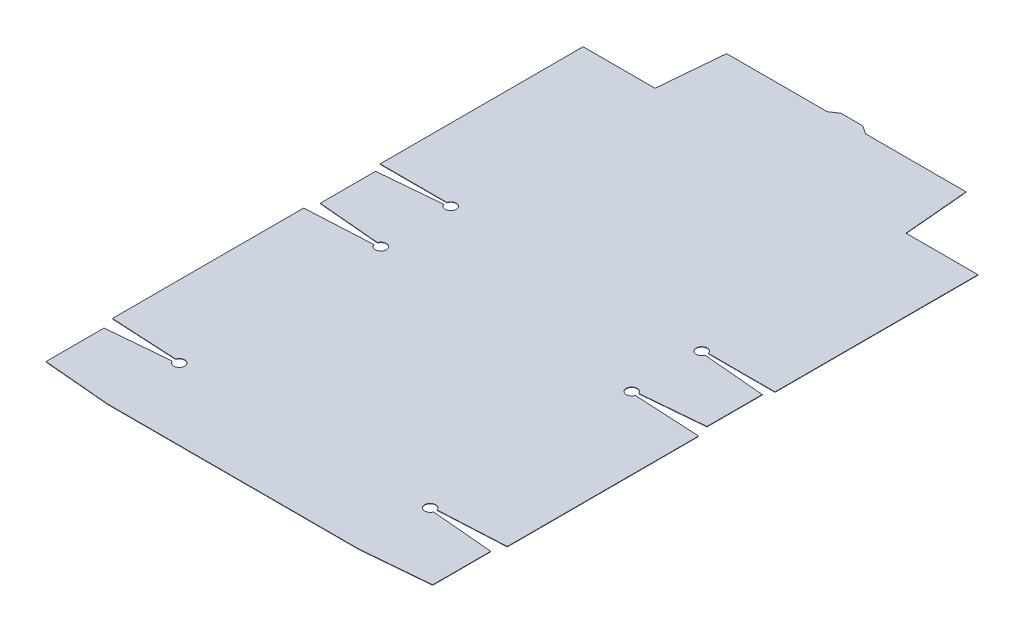
SolidWorks part; units mm, degrees
material "CHIP BOARD"
ref_plane "Front Plane" through (0, 0, 0) normal (0, 0, 1) x (1, 0, 0)
ref_plane "Top Plane" through (0, 0, 0) normal (0, 1, 0) x (1, 0, 0)
ref_plane "Right Plane" through (0, 0, 0) normal (1, 0, 0) x (0, 0, -1)
sketch "Sketch1" plane through (0, 0, 0) normal (0, 1, 0) x (1, 0, 0)
  line L0 (145.2563, 434.1812) -> (138.0341, 516.7312)
  line L1 (-146.05, 116.6813) -> (146.05, 116.6813) construction
  line L3 (145.2562, -199.2313) -> (223.8375, -192.3563)
  line L5 (-146.05, -116.6813) -> (146.05, -116.6813) construction
  line L6 (228.6, 434.1812) -> (228.6, 199.2312) construction
  line L7 (-145.2562, -199.2313) -> (145.2562, -199.2313)
  line L8 (146.05, 199.2312) -> (146.05, 116.6812) construction
  line L9 (-145.2562, -199.2313) -> (-223.8375, -192.3563)
  line L10 (228.6, -110.7237) -> (145.1732, -115.0959)
  line L11 (-228.6, -110.7237) -> (-145.1732, -115.0959)
  line L12 (-228.6, -110.7237) -> (-228.6, 110.7237)
  line L14 (223.8375, -192.3563) -> (223.8375, -125.1498)
  line L15 (223.8375, -125.1498) -> (145.1179, -118.2627)
  line L16 (-138.0341, 516.7312) -> (-145.2563, 434.1812)
  line L18 (145.2563, 434.1812) -> (228.6, 434.1812)
  line L19 (145.1179, 196.0623) -> (223.8375, 189.1752)
  line L21 (228.6, -110.7237) -> (228.6, 110.7237)
  line L22 (-145.2563, 434.1812) -> (-228.6, 434.1812)
  line L23 (228.6, 199.2312) -> (145.2562, 199.2312)
  line L24 (-228.6, 110.7237) -> (-145.1732, 115.0959)
  line L25 (223.8375, 189.1752) -> (223.8375, 125.1498)
  line L26 (228.6, 110.7237) -> (145.1732, 115.0959)
  line L27 (223.8375, 125.1498) -> (145.1179, 118.2627)
  line L28 (-228.6, 199.2312) -> (-145.2562, 199.2312)
  line L29 (0, 0) -> (0, 116.6812) construction
  line L32 (-145.1179, 196.0623) -> (-223.8375, 189.1752)
  line L33 (146.05, 116.6813) -> (146.05, -116.6813) construction
  line L34 (-146.05, 199.2312) -> (228.6, 199.2312) construction
  line L35 (145.2562, -116.6813) -> (145.2562, -199.2313) construction
  line L36 (-145.2562, -199.2313) -> (-145.2562, -116.6813) construction
  line L37 (-223.8375, 189.1752) -> (-223.8375, 125.1498)
  line L38 (-223.8375, 125.1498) -> (-145.1179, 118.2627)
  line L39 (228.6, 199.2312) -> (228.6, 434.1812)
  line L40 (-146.05, -116.6813) -> (-146.05, 116.6813) construction
  line L41 (-146.05, 116.6812) -> (-146.05, 199.2312) construction
  line L42 (-228.6, 434.1812) -> (-228.6, 199.2312) construction
  line L43 (-228.6, 434.1812) -> (228.6, 434.1812) construction
  line L44 (-138.0341, 516.7312) -> (138.0341, 516.7312)
  line L45 (0, 0) -> (-146.05, 0) construction
  line L48 (-228.6, 434.1812) -> (-228.6, 199.2312)
  line L49 (-223.8375, -192.3563) -> (-223.8375, -125.1498)
  line L50 (-223.8375, -125.1498) -> (-145.1179, -118.2627)
  arc A0 (-145.1179, -118.2627) -> (-145.1732, -115.0959) centre (-145.2562, -116.6813) ccw
  arc A1 (145.1732, -115.0959) -> (145.1179, -118.2627) centre (145.2562, -116.6813) ccw
  arc A2 (145.1179, 118.2627) -> (145.1732, 115.0959) centre (145.2562, 116.6812) ccw
  arc A3 (-145.1732, 115.0959) -> (-145.1179, 118.2627) centre (-145.2562, 116.6812) ccw
  arc A4 (-145.1179, 196.0623) -> (-145.2562, 199.2312) centre (-145.2562, 197.6437) ccw
  arc A5 (145.2562, 199.2312) -> (145.1179, 196.0623) centre (145.2562, 197.6437) ccw
  point P4 (0, 116.6812)
  dimension "D5" = 1.5875
  dimension "D3" = 82.55
  dimension "D4" = 447.675
  dimension "D6" = 93
  dimension "D7" = 5
  dimension "D8" = 233.3625
  dimension "D9" = 82.55
  dimension "D10" = 95
  dimension "D11" = 234.95
  dimension "D12" = 82.55
  dimension "D13" = 82.55
  dimension "D14" = 95
  dimension "D15" = 93
  dimension "D16" = 0.7937
  dimension "D17" = 715.9625
  dimension "D18" = 93
  dimension "D19" = 95
  dimension "D20" = 292.1
  dimension "D21" = 95
  dimension "D23" = 292.1
extrude "Extrude1" add sketch "Sketch1" along normal blind 0.4572
sketch "Sketch2" plane through (0, 0.4572, 0) normal (0, 1, 0) x (1, 0, 0)
  circle A0 centre (-145.2562, 116.6812) radius 6.35
  circle A1 centre (-145.2562, -116.6813) radius 6.35
  circle A2 centre (145.2562, -116.6813) radius 6.35
  circle A3 centre (145.2562, 116.6812) radius 6.35
  circle A4 centre (-145.2562, 197.6437) radius 6.35
  circle A5 centre (145.2562, 197.6437) radius 6.35
  arc A6 (145.1732, -115.0959) -> (145.1179, -118.2627) centre (145.2562, -116.6813) ccw construction
  arc A7 (-145.1179, 196.0623) -> (-145.2562, 199.2312) centre (-145.2562, 197.6437) ccw construction
  arc A8 (-145.1732, 115.0959) -> (-145.1179, 118.2627) centre (-145.2562, 116.6812) ccw construction
  arc A9 (-145.1179, -118.2627) -> (-145.1732, -115.0959) centre (-145.2562, -116.6813) ccw construction
  arc A10 (145.1179, 118.2627) -> (145.1732, 115.0959) centre (145.2562, 116.6812) ccw construction
  arc A11 (145.2562, 199.2312) -> (145.1179, 196.0623) centre (145.2562, 197.6437) ccw construction
  dimension "D1" = 12.7
extrude "Extrude2" cut sketch "Sketch2" against normal up to next
sketch "Sketch12" plane through (0, 0.4572, 0) normal (0, 1, 0) x (1, 0, 0)
  line L0 (-138.5896, 510.3813) -> (-22.225, 510.3813)
  line L1 (-138.0341, 516.7312) -> (-145.2563, 434.1812) construction
  line L2 (-22.225, 510.3813) -> (-12.7, 516.7312)
  line L3 (138.0341, 516.7312) -> (-138.0341, 516.7312) construction
  line L4 (12.7, 516.7312) -> (22.225, 510.3813)
  line L5 (22.225, 510.3813) -> (138.5896, 510.3813)
  line L6 (145.2563, 434.1812) -> (138.0341, 516.7312) construction
  line L7 (138.5896, 510.3813) -> (138.0341, 516.7312)
  line L8 (138.0341, 516.7312) -> (12.7, 516.7312)
  line L9 (-12.7, 516.7312) -> (-138.0341, 516.7312)
  line L10 (-138.0341, 516.7312) -> (-138.5896, 510.3813)
  dimension "D1" = 6.35
  dimension "D2" = 25.4
  dimension "D3" = 44.45
extrude "Extrude3" cut sketch "Sketch12" against normal up to next
sketch "Sketch13" plane through (0, 0.4572, 0) normal (0, 1, 0) x (1, 0, 0)
  line L0 (-61.9125, -199.2313) -> (-55.5625, -186.5313)
  line L1 (-145.2562, -199.2313) -> (145.2562, -199.2313) construction
  line L2 (-55.5625, -186.5313) -> (-49.2125, -199.2313)
  line L3 (-49.2125, -199.2313) -> (-61.9125, -199.2313)
  line L4 (49.2125, -199.2313) -> (55.5625, -186.5313)
  line L5 (55.5625, -186.5313) -> (61.9125, -199.2313)
  line L6 (49.2125, -199.2313) -> (61.9125, -199.2313)
  line L7 (-55.5625, -186.5313) -> (55.5625, -186.5313) construction
  line L8 (-55.5625, -186.5313) -> (-55.5625, -199.2313) construction
  line L9 (55.5625, -186.5313) -> (55.5625, -199.2313) construction
  line L10 (-22.225, -199.2313) -> (-12.7, -192.8813)
  line L11 (-12.7, -192.8813) -> (12.7, -192.8813)
  line L12 (12.7, -192.8813) -> (22.225, -199.2313)
  line L13 (22.225, -199.2313) -> (-22.225, -199.2313)
  point P7 (0, -186.5313)
  point P14 (0, -192.8813)
  point P17 (0, -199.2313)
  dimension "D1" = 12.7
  dimension "D2" = 111.125
  dimension "D3" = 12.7
  dimension "D4" = 6.35
  dimension "D5" = 25.4
  dimension "D6" = 44.45
extrude "Extrude4" [suppressed] cut sketch "Sketch13" against normal up to next
sheet metal parameters "Sheet-Metal1" parameters "D1"=0.7937
flatten bends "Flatten-Bends1" parameters "D1"=0
sketch "Sharp-Sketch1" plane through (0, 0.4572, 0) normal (0, 1, 0) x (-1, 0, 0)
process bends "Process-Bends1" parameters "D1"=0
sketch "Flat-Sketch1" plane through (0, 0.4572, 0) normal (0, 1, 0) x (-1, 0, 0)
sketch "Sketch3" plane through (0, 0.4572, 0) normal (0, 1, 0) x (1, 0, 0)
  line L0 (-146.05, -122.9814) -> (-146.05, -199.2313)
  line L2 (-145.2562, -199.2313) -> (145.2562, -199.2313) construction
  line L5 (-146.05, -199.2313) -> (146.05, -199.2313) construction
  line L6 (146.05, -122.9814) -> (146.05, -199.2313)
  arc A0 (151.3131, -114.7741) -> (151.2429, -118.7986) centre (145.2562, -116.6813) ccw construction
  arc A1 (-151.2429, -118.7986) -> (-151.3131, -114.7741) centre (-145.2562, -116.6813) ccw construction
  point P2 (0, -199.2313)
  dimension "D1" = 292.1
sketched bend "Sketched Bend10" [suppressed] parameters "D1"=0.7937
bend "SketchBend19" [suppressed] bend radius 0.7937 bend angle 90 parameters "D5"=7
bend "SketchBend20" [suppressed] bend radius 0 bend angle 90 parameters "D5"=8
sketch "Sketch7" plane through (0, 0.4572, 0) normal (0, 1, 0) x (1, 0, 0)
  line L0 (-146.8438, 110.5329) -> (-146.8438, -110.5329)
  line L1 (146.8438, 110.5329) -> (146.8438, -110.5329)
  line L2 (-146.8438, -110.5329) -> (146.8438, -110.5329) construction
  arc A0 (-151.3131, 114.7741) -> (-151.2429, 118.7986) centre (-145.2562, 116.6812) ccw construction
  arc A1 (151.3131, -114.7741) -> (151.2429, -118.7986) centre (145.2562, -116.6813) ccw construction
  arc A2 (-151.2429, -118.7986) -> (-151.3131, -114.7741) centre (-145.2562, -116.6813) ccw construction
  arc A4 (151.2429, 118.7986) -> (151.3131, 114.7741) centre (145.2562, 116.6812) ccw construction
  point P5 (0, -110.5329)
  dimension "D1" = 293.6875
sketch "Sketch11" plane through (0, 0.4572, 0) normal (0, 1, 0) x (1, 0, 0)
  line L0 (-146.05, 191.3436) -> (-146.05, 122.9814)
  line L1 (146.05, 191.3436) -> (146.05, 122.9814)
  line L2 (-146.05, 122.9814) -> (146.05, 122.9814) construction
  arc A0 (-151.2429, 195.5264) -> (-151.4046, 199.2312) centre (-145.2562, 197.6437) ccw construction
  arc A2 (151.4046, 199.2312) -> (151.2429, 195.5264) centre (145.2562, 197.6437) ccw construction
  arc A4 (151.2429, 118.7986) -> (151.3131, 114.7741) centre (145.2562, 116.6812) ccw construction
  arc A5 (-151.3131, 114.7741) -> (-151.2429, 118.7986) centre (-145.2562, 116.6812) ccw construction
  point P16 (0, 122.9814)
  dimension "D1" = 292.1
sketched bend "Sketched Bend9" [suppressed] parameters "D1"=0
bend "SketchBend17" bend radius 0.7937 bend angle 90 parameters "D5"=5
bend "SketchBend18" bend radius 0 bend angle 90 parameters "D5"=6
sketch "Sketch8" plane through (0, 0.4572, 0) normal (0, 1, 0) x (1, 0, 0)
  line L0 (-151.6062, 116.6813) -> (151.6062, 116.6813)
  line L1 (138.9063, -116.6813) -> (-138.9062, -116.6813)
  line L3 (0, 116.6812) -> (0, -116.6812) construction
  arc A2 (-151.2429, -118.7986) -> (-151.3131, -114.7741) centre (-145.2562, -116.6813) ccw construction
  circle A3 centre (145.2562, -116.6813) radius 6.35 construction
  arc A5 (-151.3131, 114.7741) -> (-151.2429, 118.7986) centre (-145.2562, 116.6812) ccw construction
  arc A7 (151.2429, 118.7986) -> (151.3131, 114.7741) centre (145.2562, 116.6812) ccw construction
  point P28 (0, 0)
  dimension "D1" = 233.3625
sketched bend "Sketched Bend5" [suppressed] parameters "D1"=1.5875
bend "SketchBend9" bend radius 1.5875 bend angle 90 parameters "D5"=3
bend "SketchBend10" bend radius 1.5875 bend angle 90 parameters "D5"=4
sketched bend "Sketched Bend6" [suppressed] parameters "D1"=1.5875
bend "SketchBend11" bend radius 1.5875 bend angle 90 parameters "D5"=1
bend "SketchBend12" bend radius 1.5875 bend angle 90 parameters "D5"=2
flat pattern "Flat-Pattern1" [suppressed]
sketch "Bend-Lines1" plane through (0, 0.4572, 0) normal (0, 1, 0) x (-1, 0, 0)
sketch3d "Bounding-Box1" [suppressed]
  line L0 (383.3812, -274.6375, 0) -> (383.3812, 360.3625, 0) construction
  line L1 (-89.6938, -274.6375, 0) -> (-89.6938, 360.3625, 0) construction
  line L2 (383.3812, -274.6375, 0) -> (-89.6938, -274.6375, 0) construction
  line L3 (383.3812, 360.3625, 0) -> (-89.6938, 360.3625, 0) construction
bend of the flat pattern "Flatten-<SketchBend11>1"
bend of the flat pattern "Flatten-<SketchBend12>1"
bend of the flat pattern "Flatten-<SketchBend9>1"
bend of the flat pattern "Flatten-<SketchBend10>1"
bend of the flat pattern "Flatten-<SketchBend17>1"
bend of the flat pattern "Flatten-<SketchBend18>1"
bend of the flat pattern "Flatten-<SketchBend19>1"
bend of the flat pattern "Flatten-<SketchBend20>1"
